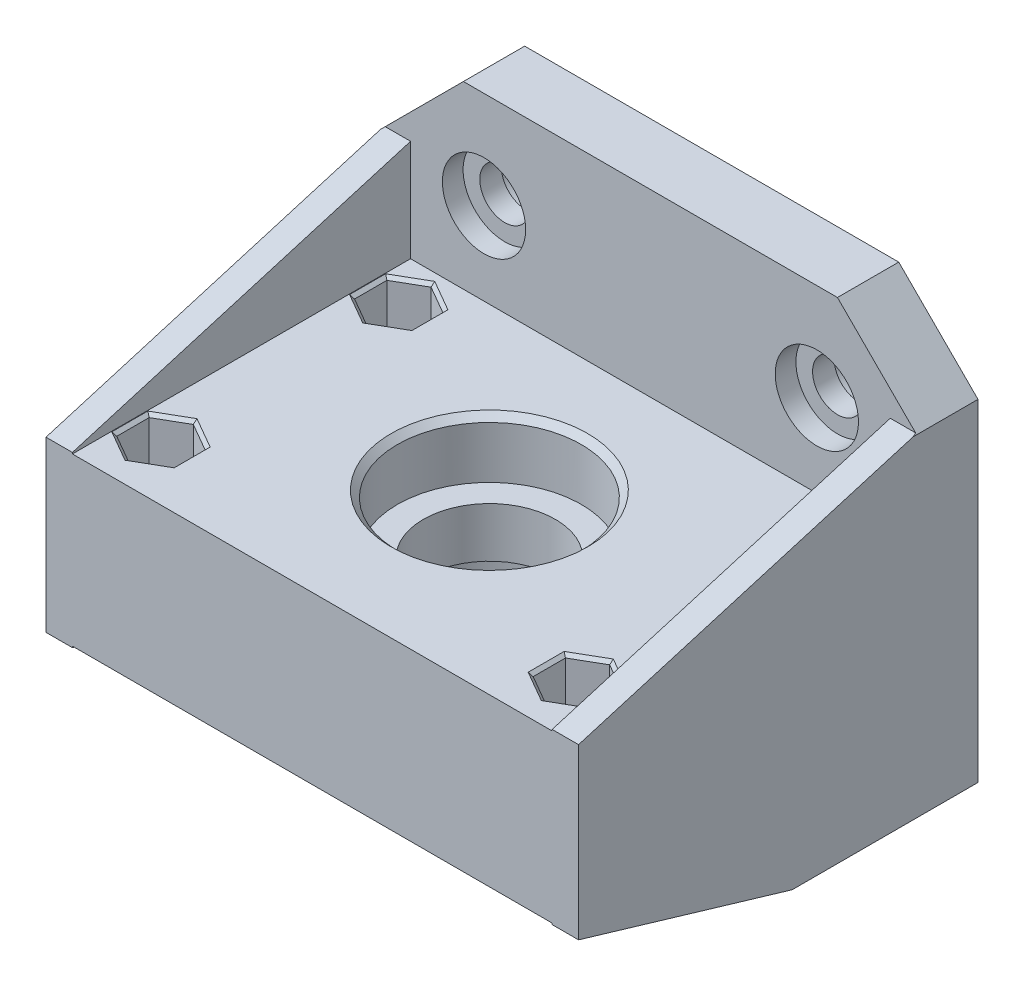
SolidWorks part; units mm, degrees
note: The reader was unsure of these and kept them because the rebuilt part matched: shared geometry of "Sketch3<3>", "Sketch12<3>".
ref_plane "Front Plane" through (0, 0, 0) normal (0, 0, 1) x (1, 0, 0)
ref_plane "Top Plane" through (0, 0, 0) normal (0, 1, 0) x (1, 0, 0)
ref_plane "Right Plane" through (0, 0, 0) normal (1, 0, 0) x (0, 0, -1)
sketch "Sketch1" plane through (0, 0, 0) normal (0, 0, 1) x (1, 0, 0)
  line L0 (0, -55) -> (0, 55) construction
  line L1 (-32.004, 29.464) -> (32.004, 29.464)
  line L2 (-32.004, 29.464) -> (-32.004, -29.464)
  line L3 (-32.004, -29.464) -> (32.004, -29.464)
  line L4 (32.004, 29.464) -> (32.004, -29.464)
  line L5 (-32.004, 29.464) -> (32.004, -29.464) construction
  line L6 (-32.004, -29.464) -> (32.004, 29.464) construction
  circle A0 centre (-20, 17.7772) radius 3
  circle A1 centre (20, 17.7772) radius 3
  circle A2 centre (0, -19.5608) radius 3
  point P0 (0, 0)
  dimension "D3" = 6
  dimension "D6" = 6
  dimension "D1" = 58.928
  dimension "D2" = 64.008
  dimension "D4" = 20
  dimension "D5" = 11.6868
  dimension "D7" = 37.338
extrude "Boss-Extrude1" add sketch "Sketch1" along normal blind 5.08
sketch "Sketch2" plane through (0, 0, 5.08) normal (0, 0, 1) x (1, 0, 0)
  line L0 (-32.004, 29.464) -> (-32.004, -29.464) construction
  line L1 (-28.829, -12.159) -> (28.829, -12.159)
  line L3 (-28.829, 7.841) -> (28.829, 7.841)
  line L6 (-32.004, -29.464) -> (32.004, -29.464) construction
  line L7 (-32.004, 20.066) -> (-32.004, -24.384)
  line L8 (-28.829, 20.066) -> (-32.004, 20.066)
  line L9 (32.004, -24.384) -> (28.829, -24.384)
  line L11 (32.004, 20.066) -> (28.829, 20.066)
  line L13 (32.004, -24.384) -> (-32.004, 20.066) construction
  line L14 (32.004, 20.066) -> (-32.004, -24.384) construction
  line L16 (28.829, -24.384) -> (28.829, -12.159)
  line L18 (-28.829, -24.384) -> (-28.829, -12.159)
  line L19 (28.829, -24.384) -> (-28.829, 20.066) construction
  line L20 (28.829, 20.066) -> (-28.829, -24.384) construction
  line L21 (-28.829, -24.384) -> (-32.004, -24.384)
  line L22 (-28.829, 7.841) -> (-28.829, 20.066)
  line L23 (28.829, 7.841) -> (28.829, 20.066)
  line L24 (32.004, 20.066) -> (32.004, -24.384)
  point P12 (0, -2.159)
  point P17 (0, -2.159)
  dimension "D2" = 17.305
  dimension "D3" = 44.45
extrude "Boss-Extrude2" add sketch "Sketch2" along normal blind 40.64
chamfer "Chamfer1" distance 40.64 distance2 12.065 4 edges at (30.4165, -24.384, 45.72) (-30.4165, -24.384, 45.72) (30.4165, 20.066, 45.72) (-30.4165, 20.066, 45.72)
sketch "Sketch3" plane through (0, 7.841, 0) normal (0, 1, 0) x (1, 0, 0)
  line L0 (28.829, -45.72) -> (-28.829, -45.72) construction
  circle A0 centre (0, -24.4348) radius 11.049
  circle A1 centre (0, -24.4348) radius 7.9375
  dimension "D1" = 22.098
  dimension "D2" = 15.875
  dimension "D3" = 21.2852
extrude "Cut-Extrude1" cut sketch "Sketch3" against normal blind 40.64 contours A1
extrude "Cut-Extrude2" cut sketch "Sketch3<3>" against normal blind 7
sketch "Sketch3<3>" plane through (0, 7.841, 0) normal (0, 1, 0) x (1, 0, 0) same geometry as "Sketch3"
ref_plane "Plane1" through (0, -2.159, 0) normal (0, 1, 0) x (1, 0, 0)
mirror "Mirror2" about plane through (0, -2.159, 0) normal (0, 1, 0) of "Cut-Extrude2"
fillet "Fillet1" radius 0.762 2 edges at (-11.049, 7.841, 24.4348) (-11.049, -12.159, 24.4348) profile chamfer
sketch "Sketch4" plane through (0, 7.841, 0) normal (0, 1, 0) x (1, 0, 0)
  line L0 (-28.829, -45.72) -> (-28.829, -5.08) construction
  line L1 (-25.019, -14.1969) -> (-21.6535, -12.2539)
  line L2 (-21.6535, -12.2539) -> (-21.6535, -8.3677)
  line L3 (-21.6535, -8.3677) -> (-25.019, -6.4247)
  line L4 (-25.019, -6.4247) -> (-28.3845, -8.3677)
  line L5 (-28.3845, -8.3677) -> (-28.3845, -12.2539)
  line L6 (-28.3845, -12.2539) -> (-25.019, -14.1969)
  line L7 (-25.019, -42.7719) -> (-21.6535, -40.8289)
  line L8 (-21.6535, -40.8289) -> (-21.6535, -36.9427)
  line L9 (-21.6535, -36.9427) -> (-25.019, -34.9997)
  line L10 (-25.019, -34.9997) -> (-28.3845, -36.9427)
  line L11 (-28.3845, -36.9427) -> (-28.3845, -40.8289)
  line L12 (-28.3845, -40.8289) -> (-25.019, -42.7719)
  line L13 (0, -25.146) -> (0, 25.146) construction
  line L14 (28.3845, -40.8289) -> (25.019, -42.7719)
  line L15 (28.3845, -36.9427) -> (28.3845, -40.8289)
  line L16 (25.019, -34.9997) -> (28.3845, -36.9427)
  line L17 (21.6535, -36.9427) -> (25.019, -34.9997)
  line L18 (21.6535, -40.8289) -> (21.6535, -36.9427)
  line L19 (25.019, -42.7719) -> (21.6535, -40.8289)
  line L20 (28.3845, -12.2539) -> (25.019, -14.1969)
  line L21 (28.3845, -8.3677) -> (28.3845, -12.2539)
  line L22 (25.019, -6.4247) -> (28.3845, -8.3677)
  line L23 (21.6535, -8.3677) -> (25.019, -6.4247)
  line L24 (21.6535, -12.2539) -> (21.6535, -8.3677)
  line L25 (25.019, -14.1969) -> (21.6535, -12.2539)
  circle A0 centre (-25.019, -10.3108) radius 3.3655 construction
  dimension "D1" = 3.81
  dimension "D2" = 2
extrude "Cut-Extrude3" cut sketch "Sketch4" against normal blind 6.35
sketch "Sketch5" plane through (0, 1.491, 0) normal (0, 1, 0) x (1, 0, 0)
  line L0 (-25.019, -6.4247) -> (-25.019, -14.1969)
  line L1 (-28.3845, -40.8289) -> (-21.6535, -36.9427)
  line L2 (0, -25.146) -> (0, 25.146) construction
  circle A0 centre (-25.019, -10.3108) radius 2.159
  circle A1 centre (-25.019, -38.8858) radius 2.159
  circle A2 centre (25.019, -10.3108) radius 2.159
  circle A3 centre (25.019, -38.8858) radius 2.159
extrude "Cut-Extrude4" cut sketch "Sketch5" against normal blind 25.4 contours L0 A0 | L0 A0 | L1 A1 | L1 A1 | A2 | A3
sketch "Sketch6" plane through (0, -12.159, 0) normal (0, -1, 0) x (1, 0, 0)
  circle A0 centre (-25.019, 38.8858) radius 5.08
  circle A1 centre (25.019, 38.8858) radius 5.08
  circle A2 centre (25.019, 10.3108) radius 5.08
  circle A3 centre (-25.019, 10.3108) radius 5.08
extrude "Cut-Extrude5" cut sketch "Sketch6" against normal blind 5.08 and the other way blind 25.4
chamfer "Chamfer2" distance 0.381 angle 45 24 edges at (21.6535, 7.841, 38.8858) (23.3362, 7.841, 41.8004) (26.7017, 7.841, 41.8004) (28.3845, 7.841, 38.8858) (26.7017, 7.841, 35.9712) (23.3362, 7.841, 35.9712) (-26.7017, 7.841, 35.9712) (-28.3845, 7.841, 38.8858) (-26.7017, 7.841, 41.8004) (-23.3362, 7.841, 41.8004) (-21.6535, 7.841, 38.8858) (-23.3362, 7.841, 35.9712) (26.7018, 7.841, 7.3962) (28.3845, 7.841, 10.3108) (26.7018, 7.841, 13.2254) (23.3363, 7.841, 13.2254) (21.6535, 7.841, 10.3108) (23.3363, 7.841, 7.3962) (-28.3845, 7.841, 10.3108) (-26.7018, 7.841, 13.2254) (-23.3363, 7.841, 13.2254) (-21.6535, 7.841, 10.3108) (-23.3363, 7.841, 7.3962) (-26.7018, 7.841, 7.3962)
sketch "Sketch7" plane through (0, 0, 5.08) normal (0, 0, 1) x (1, 0, 0)
  circle A0 centre (-20, 17.7772) radius 5.0038
  circle A1 centre (20, 17.7772) radius 5.0038
  circle A2 centre (0, -19.5608) radius 5.0038
  dimension "D1" = 10.0076
  dimension "D2" = 10.0076
extrude "Cut-Extrude6" cut sketch "Sketch7" against normal blind 2.4892
sketch "Sketch8" plane through (0, 0, 5.08) normal (0, 0, 1) x (1, 0, 0)
  line L0 (32.004, 29.464) -> (-32.004, 29.464) construction
  line L1 (-6.5405, 47.244) -> (6.5405, 47.244)
  line L2 (-6.5405, 47.244) -> (-6.5405, 11.684)
  line L3 (-6.5405, 11.684) -> (6.5405, 11.684)
  line L4 (6.5405, 47.244) -> (6.5405, 11.684)
  line L5 (-6.5405, 47.244) -> (6.5405, 11.684) construction
  line L6 (-6.5405, 11.684) -> (6.5405, 47.244) construction
  point P0 (0, 29.464)
  dimension "D1" = 13.081
  dimension "D2" = 35.56
sketch "Sketch9" plane through (0, 0, 5.08) normal (0, 0, 1) x (1, 0, 0)
  line L1 (-40.0363, 31.4785) -> (40.0363, 31.4785)
  line L2 (-40.0363, 31.4785) -> (-40.0363, -31.4785)
  line L3 (-40.0363, -31.4785) -> (40.0363, -31.4785)
  line L4 (40.0363, 31.4785) -> (40.0363, -31.4785)
  line L5 (-40.0363, 31.4785) -> (40.0363, -31.4785) construction
  line L6 (-40.0363, -31.4785) -> (40.0363, 31.4785) construction
  point P0 (0, 0)
sketch "Sketch10" plane through (0, 0, 0) normal (0, 0, -1) x (-1, 0, 0)
  line L8 (-32.004, 29.464) -> (-32.004, -29.464)
  line L9 (-32.004, -29.464) -> (32.004, -29.464)
  line L10 (32.004, -29.464) -> (32.004, 29.464)
  line L11 (32.004, 29.464) -> (-32.004, 29.464)
  line L12 (-32.004, 29.464) -> (-32.004, -29.464)
  line L13 (-32.004, -29.464) -> (32.004, -29.464)
  line L14 (32.004, -29.464) -> (32.004, 29.464)
  line L15 (32.004, 29.464) -> (-32.004, 29.464)
  circle A0 centre (-20, 17.7772) radius 4.191
  circle A1 centre (20, 17.7772) radius 4.191
  circle A2 centre (0, -19.5608) radius 4.191
  dimension "D1" = 0
extrude "Boss-Extrude3" add sketch "Sketch10" along normal blind 2.286
sketch "Sketch12" plane through (0, 0, -2.286) normal (0, 0, -1) x (-1, 0, 0)
  line L0 (32.004, -29.464) -> (-32.004, -29.464) construction
  line L1 (8.9754, -22.479) -> (13.3777, -30.104)
  line L2 (12.6416, -22.479) -> (15.2108, -26.929)
  line L3 (15.2108, -26.929) -> (20.3492, -26.929)
  line L4 (20.3492, -26.929) -> (22.9184, -22.479)
  line L5 (22.9184, -22.479) -> (20.3492, -18.029)
  line L6 (20.3492, -18.029) -> (15.2108, -18.029)
  line L7 (15.2108, -18.029) -> (12.6416, -22.479)
  line L8 (13.3777, -30.104) -> (22.1823, -30.104)
  line L9 (22.1823, -30.104) -> (26.5846, -22.479)
  line L10 (26.5846, -22.479) -> (22.1823, -14.854)
  line L11 (22.1823, -14.854) -> (13.3777, -14.854)
  line L12 (13.3777, -14.854) -> (8.9754, -22.479)
  line L13 (32.004, 29.464) -> (32.004, -29.464)
  line L14 (32.004, 0) -> (-33.5375, 0)
  line L15 (22.1823, -30.104) -> (36.7481, -4.8753)
  line L16 (36.7481, -4.8753) -> (41.5726, -34.3126)
  line L17 (41.5726, -34.3126) -> (22.1823, -30.104)
  line L18 (0, 26.4033) -> (0, -26.4033) construction
  line L19 (-15.2108, -18.029) -> (-12.6416, -22.479)
  line L20 (-20.3492, -18.029) -> (-15.2108, -18.029)
  line L21 (-22.9184, -22.479) -> (-20.3492, -18.029)
  line L22 (-20.3492, -26.929) -> (-22.9184, -22.479)
  line L23 (-15.2108, -26.929) -> (-20.3492, -26.929)
  line L24 (-12.6416, -22.479) -> (-15.2108, -26.929)
  line L25 (-13.3777, -14.854) -> (-8.9754, -22.479)
  line L26 (-22.1823, -14.854) -> (-13.3777, -14.854)
  line L27 (-26.5846, -22.479) -> (-22.1823, -14.854)
  line L28 (-22.1823, -30.104) -> (-26.5846, -22.479)
  line L29 (-13.3777, -30.104) -> (-22.1823, -30.104)
  line L30 (-8.9754, -22.479) -> (-13.3777, -30.104)
  circle A0 centre (17.78, -22.479) radius 2.2225
  circle A1 centre (17.78, -22.479) radius 4.45 construction
  circle A2 centre (-17.78, -22.479) radius 2.2225
  line M4 (-32.004, -29.464) -> (32.004, -29.464)
  dimension "D1" = 4.445
  dimension "D2" = 17.78
  dimension "D3" = 6.985
  dimension "D4" = 3.175
extrude "Boss-Extrude4" add sketch "Sketch12" against normal blind 8.89 contours L11 L12 L1 L9 L10 L7 L6 L5 L4 L3 L2 M4 | L30 L25 L26 L27 L28 L19 L24 L23 L22 L21 L20 M4
sketch "Sketch13" plane through (0, 0, 5.08) normal (0, 0, 1) x (1, 0, 0)
  line L6 (0, 0) -> (0, -9.0684)
  line L7 (20.3492, -26.929) -> (15.2108, -26.929)
  line L8 (22.9184, -22.479) -> (20.3492, -26.929)
  line L9 (20.3492, -18.029) -> (22.9184, -22.479)
  line L10 (15.2108, -18.029) -> (20.3492, -18.029)
  line L11 (12.6416, -22.479) -> (15.2108, -18.029)
  line L12 (-15.2108, -26.929) -> (-12.6416, -22.479)
  line L13 (-12.6416, -22.479) -> (-15.2108, -18.029)
  line L14 (-15.2108, -18.029) -> (-20.3492, -18.029)
  line L15 (-20.3492, -18.029) -> (-22.9184, -22.479)
  line L16 (-22.9184, -22.479) -> (-20.3492, -26.929)
  line L17 (-20.3492, -26.929) -> (-15.2108, -26.929)
  line L18 (-15.2108, -26.929) -> (-12.6416, -22.479)
  line L19 (-12.6416, -22.479) -> (-15.2108, -18.029)
  line L20 (-15.2108, -18.029) -> (-20.3492, -18.029)
  line L21 (-20.3492, -18.029) -> (-22.9184, -22.479)
  line L22 (-22.9184, -22.479) -> (-20.3492, -26.929)
  line L23 (-20.3492, -26.929) -> (-15.2108, -26.929)
  line L24 (15.2108, -26.929) -> (12.6416, -22.479)
  dimension "D1" = 0
extrude "Cut-Extrude7" cut sketch "Sketch13" against normal blind 2.54 contours L19 L20 L21 L22 L23 L18 | L9 L8 L7 L24 L11 L10
extrude "Cut-Extrude8" cut sketch "Sketch12<3>" against normal through all both and the other way through all contours A0 | A2
sketch "Sketch12<3>" plane through (0, 0, -2.286) normal (0, 0, -1) x (-1, 0, 0) same geometry as "Sketch12"
chamfer "Chamfer3" distance 9.525 angle 45 4 edges at (-32.004, -29.464, 1.397) (-32.004, 29.464, 1.397) (32.004, 29.464, 1.397) (32.004, -29.464, 1.397)
chamfer "Chamfer4" distance 0.9525 angle 45 25 edges at (-24.3834, -18.6665, 6.604) (-17.78, -14.854, 6.604) (-11.1766, -18.6665, 6.604) (-10.9918, -25.9715, 6.604) (-17.7436, -29.464, 6.604) (-22.5651, -29.3779, 6.604) (-24.6179, -25.8854, 6.604) (-17.78, -18.029, 6.604) (-21.6338, -20.254, 6.604) (-21.6338, -24.704, 6.604) (-17.78, -26.929, 6.604) (-13.9262, -24.704, 6.604) (-13.9262, -20.254, 6.604) (13.9262, -24.704, 6.604) (17.78, -26.929, 6.604) (21.6338, -24.704, 6.604) (21.6338, -20.254, 6.604) (17.78, -18.029, 6.604) (13.9262, -20.254, 6.604) (10.9918, -25.9715, 6.604) (11.1766, -18.6665, 6.604) (17.78, -14.854, 6.604) (24.3834, -18.6665, 6.604) (24.6179, -25.8854, 6.604) (17.7436, -29.464, 6.604)
